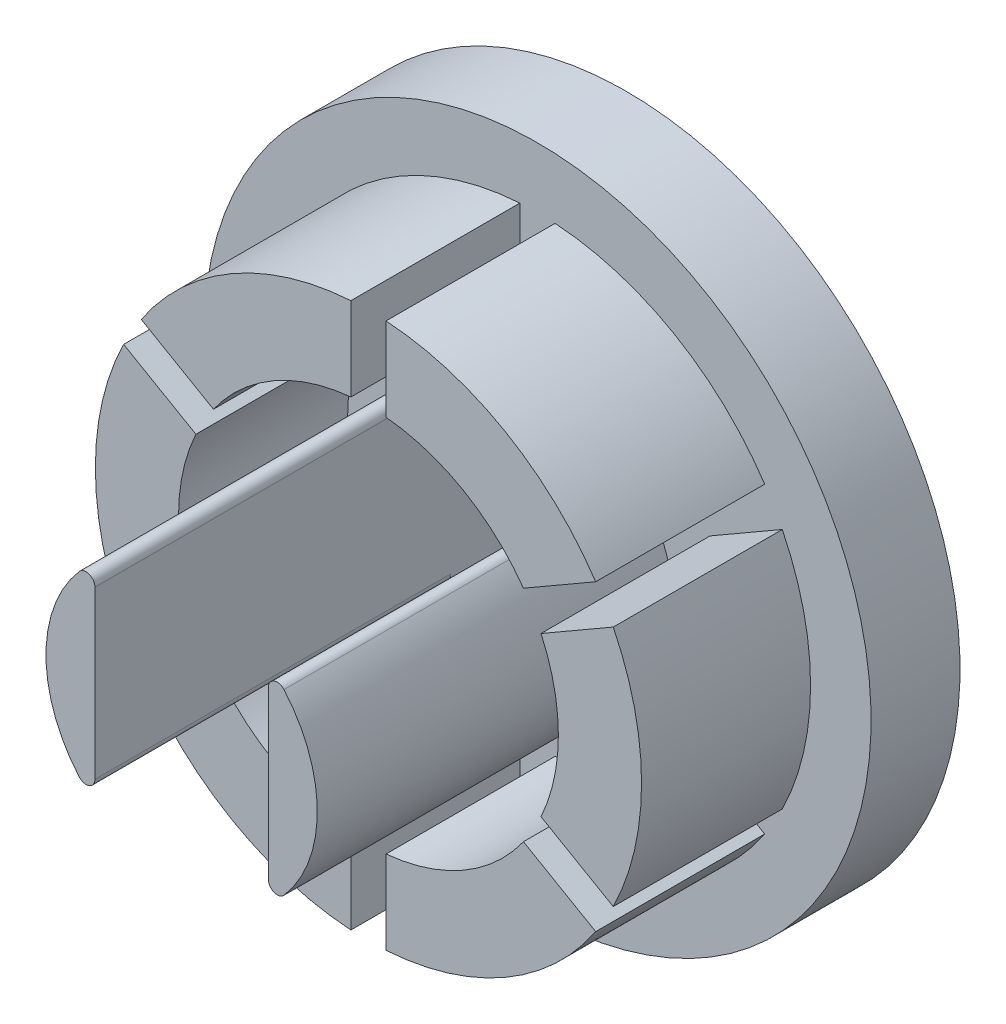
SolidWorks part; units mm, degrees
ref_plane "Plano frontal" through (0, 0, 0) normal (0, 0, 1) x (1, 0, 0)
ref_plane "Plano superior" through (0, 0, 0) normal (0, 1, 0) x (1, 0, 0)
ref_plane "Plano direito" through (0, 0, 0) normal (1, 0, 0) x (0, 0, -1)
sketch "Esboço1" plane through (0, 0, 0) normal (0, 0, 1) x (1, 0, 0)
  line L0 (1.85, 1.9666) -> (1.85, -1.9666) construction
  line L1 (-1.85, -1.9666) -> (-1.85, 1.9666) construction
  arc A0 (-1.85, -1.9666) -> (1.85, -1.9666) centre (0, 0) ccw construction
  arc A1 (1.85, 1.9666) -> (-1.85, 1.9666) centre (0, 0) ccw construction
  circle A2 centre (0, 0) radius 3.05 construction
sketch "Esboço2" plane through (0, 0, 0) normal (0, 0, 1) x (1, 0, 0)
  line L4 (1.95, -2.0094) -> (1.95, 2.0094)
  line L5 (-1.95, 2.0094) -> (-1.95, -2.0094)
  line L6 (1.95, -1.8708) -> (1.95, 1.8708)
  line L7 (-1.95, 1.8708) -> (-1.95, -1.8708)
  arc A7 (-1.95, -2.0094) -> (1.95, -2.0094) centre (0, 0) ccw
  arc A8 (1.95, 2.0094) -> (-1.95, 2.0094) centre (0, 0) ccw
  arc A16 (-2.3009, 2.0021) -> (-2.3009, -2.0021) centre (0, 0) ccw
  arc A17 (2.3009, -2.0021) -> (2.3009, 2.0021) centre (0, 0) ccw
  arc A18 (1.95, 1.8708) -> (2.3009, 2.0021) centre (2.15, 1.8708) cw
  arc A19 (1.95, -1.8708) -> (2.3009, -2.0021) centre (2.15, -1.8708) ccw
  arc A20 (-1.95, -1.8708) -> (-2.3009, -2.0021) centre (-2.15, -1.8708) cw
  arc A21 (-1.95, 1.8708) -> (-2.3009, 2.0021) centre (-2.15, 1.8708) ccw
  point P9 (1.95, -2.3452)
  dimension "D1" = 6.1
  dimension "D3" = 0.2
  dimension "D2" = 0.1
extrude "Ressalto-extrusão1" add sketch "Esboço2" along normal blind 8
sketch "Esboço3" plane through (0, 0, 0) normal (0, 0, -1) x (-1, 0, 0)
  circle A0 centre (0, 0) radius 7.5
  circle A5 centre (0, 0) radius 1.475
  circle A6 centre (0, 0) radius 0.975 construction
  dimension "D1" = 1.95
  dimension "D2" = 0.5
  dimension "D3" = 15
extrude "Ressalto-extrusão2" add sketch "Esboço3" along normal blind 2
sketch "Esboço4" plane through (0, 0, -2) normal (0, 0, -1) x (-1, 0, 0)
  line L0 (0, 0) -> (0, 6.26) construction
  line L1 (-0.275, 6.254) -> (-0.275, 4.1409) construction
  line L3 (0.275, 4.1409) -> (0.275, 6.254) construction
  line L5 (5.2786, 3.3651) -> (3.4486, 2.3086) construction
  line L6 (3.7236, 1.8323) -> (5.5536, 2.8888) construction
  line L7 (5.5536, -2.8888) -> (3.7236, -1.8323) construction
  line L8 (3.4486, -2.3086) -> (5.2786, -3.3651) construction
  line L9 (0.275, -6.254) -> (0.275, -4.1409) construction
  line L10 (-0.275, -4.1409) -> (-0.275, -6.254) construction
  line L11 (-5.2786, -3.3651) -> (-3.4486, -2.3086) construction
  line L12 (-3.7236, -1.8323) -> (-5.5536, -2.8888) construction
  line L13 (-5.5536, 2.8888) -> (-3.7236, 1.8323) construction
  line L14 (-3.4486, 2.3086) -> (-5.2786, 3.3651) construction
  circle A0 centre (0, 0) radius 8.9 construction
  circle A1 centre (0, 0) radius 6.26 construction
  circle A2 centre (0, 0) radius 4.15 construction
  point P32 (0, 0)
  dimension "D1" = 17.8
  dimension "D2" = 2.64
  dimension "D3" = 8.3
  dimension "D4" = 0.275
  dimension "D5" = 0.275
  dimension "D6" = 6
sketch "Esboço7" plane through (0, 0, 0) normal (0, 0, 1) x (1, 0, 0)
  line L0 (-5.1089, 3.4057) -> (-3.4846, 2.4679)
  line L9 (-0.395, 4.2517) -> (-0.395, 6.1273)
  line L10 (0.395, 6.1273) -> (0.395, 4.2517)
  line L11 (3.4846, 2.4679) -> (5.1089, 3.4057)
  line L12 (5.5039, 2.7216) -> (3.8796, 1.7838)
  line L13 (3.8796, -1.7838) -> (5.5039, -2.7216)
  line L14 (5.1089, -3.4057) -> (3.4846, -2.4679)
  line L15 (0.395, -4.2517) -> (0.395, -6.1273)
  line L16 (-0.395, -6.1273) -> (-0.395, -4.2517)
  line L17 (-3.4846, -2.4679) -> (-5.1089, -3.4057)
  line L18 (-5.5039, -2.7216) -> (-3.8796, -1.7838)
  line L19 (-3.8796, 1.7838) -> (-5.5039, 2.7216)
  arc A6 (-0.395, 6.1273) -> (-5.1089, 3.4057) centre (0, 0) ccw
  arc A7 (-0.395, 4.2517) -> (-3.4846, 2.4679) centre (0, 0) ccw
  arc A8 (5.1089, 3.4057) -> (0.395, 6.1273) centre (0, 0) ccw
  arc A9 (3.4846, 2.4679) -> (0.395, 4.2517) centre (0, 0) ccw
  arc A10 (5.5039, -2.7216) -> (5.5039, 2.7216) centre (0, 0) ccw
  arc A11 (3.8796, -1.7838) -> (3.8796, 1.7838) centre (0, 0) ccw
  arc A12 (0.395, -6.1273) -> (5.1089, -3.4057) centre (0, 0) ccw
  arc A13 (0.395, -4.2517) -> (3.4846, -2.4679) centre (0, 0) ccw
  arc A14 (-5.1089, -3.4057) -> (-0.395, -6.1273) centre (0, 0) ccw
  arc A15 (-3.4846, -2.4679) -> (-0.395, -4.2517) centre (0, 0) ccw
  arc A16 (-5.5039, 2.7216) -> (-5.5039, -2.7216) centre (0, 0) ccw
  arc A17 (-3.8796, 1.7838) -> (-3.8796, -1.7838) centre (0, 0) ccw
  point P28 (0, 0)
  dimension "D1" = 6
extrude "Ressalto-extrusão3" add sketch "Esboço7" along normal blind 3.8
sketch "Esboço10" plane through (0, 0, 0) normal (0, 0, 1) x (1, 0, 0)
  line L1 (-1.95, -1.8708) -> (-1.95, 1.8708) construction
  line L2 (1.95, 2.0403) -> (1.95, -2.0403)
  line L3 (-1.95, -2.0403) -> (-1.95, 2.0403)
  arc A2 (1.95, 2.0403) -> (-1.95, 2.0403) centre (0, 0) ccw
  arc A3 (-1.95, -2.0403) -> (1.95, -2.0403) centre (0, 0) ccw
extrude "Corte-extrusão2" cut sketch "Esboço10" against normal blind 10 contours A2 L3 A3 L2
